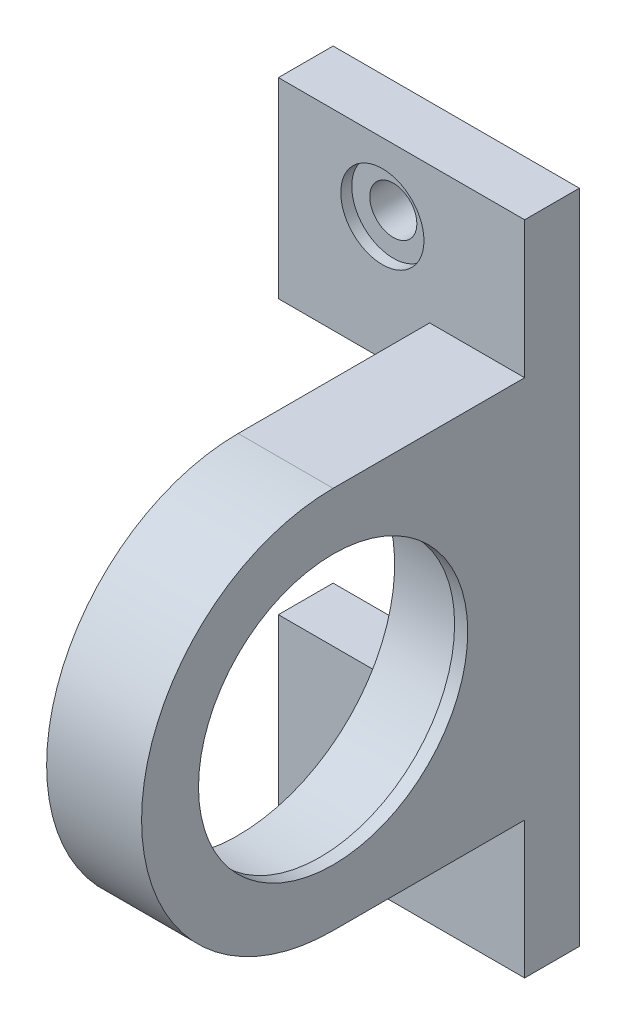
SolidWorks part; units mm, degrees
ref_plane "前视基准面" through (0, 0, 0) normal (0, 0, 1) x (1, 0, 0)
ref_plane "上视基准面" through (0, 0, 0) normal (0, 1, 0) x (1, 0, 0)
ref_plane "右视基准面" through (0, 0, 0) normal (1, 0, 0) x (0, 0, -1)
sketch "草图2" plane through (0, 0, 0) normal (0, 0, 1) x (1, 0, 0)
  line L0 (-14.7736, 24.3382) -> (-14.7736, -35.6618)
  line L1 (-14.7736, -35.6618) -> (30.2264, -35.6618)
  line L2 (7.7264, -35.6618) -> (7.7264, -18.1618)
  line L3 (21.55, -18.1618) -> (-6.0971, -18.1618)
  line L4 (-6.0971, -18.1618) -> (-6.0971, 6.8382)
  line L5 (-6.0971, 6.8382) -> (21.55, 6.8382)
  line L6 (7.7264, 6.8382) -> (7.7264, 24.3382)
  line L7 (30.2264, 24.3382) -> (-14.7736, 24.3382)
  line L8 (7.7264, 28.8603) -> (7.7264, -39.8897) construction
  line L9 (21.55, -18.1618) -> (21.55, 6.8382)
  line L10 (30.2264, 24.3382) -> (30.2264, -35.6618)
  line L11 (-18.1559, -5.6618) -> (33.2411, -5.6618) construction
  line L12 (44.0218, -5.6618) -> (44.0218, 26.2521) construction
  point P16 (-6.0971, -5.6618)
  point P17 (-14.7736, -5.6618)
  dimension "D1" = 45
  dimension "D2" = 25
  dimension "D3" = 60
extrude "凸台-拉伸2" add sketch "草图2" along normal blind 5 contours L6 L7 L0 L1 L2 L3 L4 L5 | L10 L7 L6 L5 L9 L3 L2 L1 region at (-3.5236, 23.6974, 0) region at (18.9764, 23.6974, 0)
sketch "草图4" plane through (0, 0, 5) normal (0, 0, 1) x (1, 0, 0)
  line L0 (-18.165, -5.6618) -> (33.9165, -5.6618) construction
  line L1 (-14.7736, 24.3382) -> (-14.7736, -35.6618) construction
  line L2 (-14.7736, -23.1618) -> (-6.0971, -23.1618)
  line L3 (-14.7736, -23.1618) -> (-14.7736, 11.8382)
  line L4 (-14.7736, 11.8382) -> (-6.0971, 11.8382)
  line L5 (-6.0971, -23.1618) -> (-6.0971, 11.8382)
  line L6 (-6.0971, -18.1618) -> (-6.0971, 6.8382) construction
  line L7 (7.7264, -39.813) -> (7.7264, 28.1228) construction
  line L8 (30.2264, 11.8382) -> (21.55, 11.8382)
  line L9 (21.55, -23.1618) -> (21.55, 11.8382)
  line L10 (30.2264, -23.1618) -> (21.55, -23.1618)
  line L11 (30.2264, -23.1618) -> (30.2264, 11.8382)
  point P17 (-14.7736, -5.6618)
  dimension "D1" = 35
extrude "凸台-拉伸15" add sketch "草图4" along normal blind 35
sketch "草图5" plane through (-14.7736, 0, 0) normal (-1, 0, 0) x (0, 0, 1)
  line L0 (0, -5.6618) -> (40, -5.6618)
  line L1 (0, 24.3382) -> (0, -35.6618) construction
  line L2 (40, 11.8382) -> (40, -23.1618) construction
  line L3 (22.5, 11.8382) -> (40, 11.8382)
  line L4 (40, 11.8382) -> (40, -23.1618)
  line L5 (40, -23.1618) -> (22.5, -23.1618)
  circle A0 centre (22.5, -5.6618) radius 17.5
  line M5 (5, -23.1618) -> (40, -23.1618)
  line M6 (40, -23.1618) -> (40, 11.8382)
  line M7 (40, 11.8382) -> (5, 11.8382)
  dimension "D1" = 35
extrude "切除-拉伸1" cut sketch "草图5" against normal blind 45 contours A0 M5 M6 | A0 M6 M7 region at (-14.7736, 7.9293, 36.0911) region at (-14.7736, -19.2528, 36.0911)
sketch "草图6" plane through (-14.7736, 0, 0) normal (-1, 0, 0) x (0, 0, 1)
  circle A0 centre (22.5, -5.6618) radius 14.3
  dimension "D1" = 28.6
extrude "切除-拉伸2" cut sketch "草图6" against normal blind 45
fillet "圆角1" radius 5 4 edges at (-6.0971, 6.8382, 2.5) (21.55, 6.8382, 2.5) (-6.0971, -18.1618, 2.5) (21.55, -18.1618, 2.5)
sketch "草图7" plane through (-6.0971, 0, 0) normal (1, 0, 0) x (0, 0, -1)
  circle A0 centre (-22.5, -5.6618) radius 15
  circle A1 centre (-22.5, -5.6618) radius 13
extrude "凸台-拉伸16" add sketch "草图7" against normal blind 1
sketch "草图8" plane through (21.55, 0, 0) normal (-1, 0, 0) x (0, 0, 1)
  circle A0 centre (22.5, -5.6618) radius 15
  circle A1 centre (22.5, -5.6618) radius 10
sketch "草图9" plane through (0, 0, 5) normal (0, 0, 1) x (1, 0, 0)
  line L0 (7.7264, 24.3382) -> (7.7264, -35.6618)
  line L13 (30.2264, 24.3382) -> (-14.7736, 24.3382) construction
  line L14 (-14.7736, -35.6618) -> (30.2264, -35.6618) construction
sketch "草图11" plane through (0, 0, 5) normal (0, 0, 1) x (1, 0, 0)
  line L0 (-14.7736, 18.0882) -> (30.2264, 18.0882)
  line L1 (-14.7736, 24.3382) -> (-14.7736, 11.8382) construction
  line L2 (30.2264, 24.3382) -> (30.2264, 11.8382) construction
  line L3 (7.7264, 24.3382) -> (7.7264, -35.6618) construction
  line L4 (30.2264, 24.3382) -> (-14.7736, 24.3382) construction
  line L5 (-14.7736, -35.6618) -> (30.2264, -35.6618) construction
  line L6 (7.7264, -5.6618) -> (45.6912, -5.6618) construction
  line L10 (-14.7736, -29.4118) -> (30.2264, -29.4118)
  line L11 (-14.7736, -23.1618) -> (-14.7736, -35.6618) construction
  point P4 (-1.7736, 18.0882)
  point P16 (-1.7736, -29.4118)
  point P18 (17.2264, -29.4118)
  point P25 (17.2264, 18.0882)
  dimension "D1" = 13
split "分割1" trim tools "草图9" bodies to split 111 resulting bodies 117 118
delete or keep bodies "实体-删除/保留 2" type delete bodies bodies 117
hole_wizard "打孔尺寸(%根据六角头螺)栓 全螺纹的类型1" positions "3D草图2" profile "草图13" counterbore size "M4" standard "GB"
sketch3d "3D草图2"
  point P0 (17.2264, 18.0882, 5)
  point P3 (17.2264, -29.4118, 5)
sketch "草图13" plane through (17.2264, 18.0882, 5) normal (1, 0, 0) x (0, -1, 0)
  line L0 (0, 0) -> (0, 6.2919)
  line L1 (0, 6.2919) -> (2.15, 5)
  line L2 (2.15, 5) -> (2.15, 1)
  line L3 (2.15, 1) -> (3.8, 1)
  line L4 (3.8, 1) -> (3.8, 0)
  line L5 (3.8, 0) -> (0, 0)
  line L10 (0, 6.2919) -> (-2.15, 5) construction
  line L11 (0, -6.35) -> (0, 107.95) construction
  dimension "孔直径" = 4.3
  dimension "孔深度" = 5
  dimension "柱形沉头孔直径" = 7.6
  dimension "柱形沉头孔深度" = 1
  dimension "导头角度" = 118
sketch "草图14" plane through (30.2264, 0, 0) normal (1, 0, 0) x (0, 0, -1)
  circle A0 centre (-22.5, -5.6618) radius 14.3 construction
  circle A1 centre (-22.5, -5.6618) radius 14.3
extrude "拉伸-薄壁1" add sketch "草图14" against normal blind 1.2 thin thin type one direction reverse wall 2
